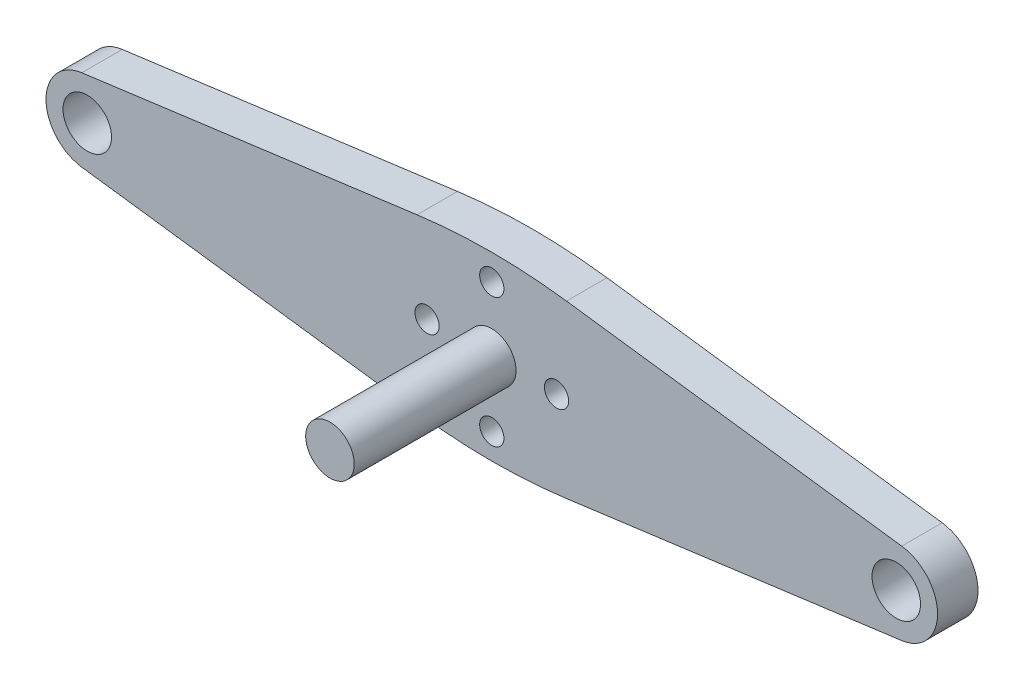
SolidWorks part; units mm, degrees
material "ABS"
ref_plane "Płaszczyzna przednia" through (0, 0, 0) normal (0, 0, 1) x (1, 0, 0)
ref_plane "Płaszczyzna górna" through (0, 0, 0) normal (0, 1, 0) x (1, 0, 0)
ref_plane "Płaszczyzna prawa" through (0, 0, 0) normal (1, 0, 0) x (0, 0, -1)
sketch "Szkic1" plane through (0, 0, 0) normal (0, 0, 1) x (1, 0, 0)
  line L0 (-44.521, 0) -> (57.4684, 0) construction
  line L1 (0, 0) -> (0, 26.3225) construction
  line L2 (-50.6729, 5.0557) -> (-9.2351, 10.5708)
  line L3 (-50.6729, -5.0557) -> (-9.2351, -10.5708)
  line L4 (50.6729, -5.0557) -> (9.2351, -10.5708)
  line L5 (50.6729, 5.0557) -> (9.2351, 10.5708)
  circle A0 centre (0, 0) radius 3
  circle A1 centre (0, 8) radius 1.5
  circle A2 centre (-8, 0) radius 1.5
  circle A3 centre (8, 0) radius 1.5
  circle A4 centre (0, -8) radius 1.5
  circle A5 centre (-50, 0) radius 3
  circle A6 centre (50, 0) radius 3
  arc A7 (-50.6729, 5.0557) -> (-50.6729, -5.0557) centre (-50, 0) ccw
  arc A8 (50.6729, 5.0557) -> (50.6729, -5.0557) centre (50, 0) cw
  arc A9 (-9.2351, 10.5708) -> (9.2351, 10.5708) centre (0, -58.8174) cw
  arc A10 (-9.2351, -10.5708) -> (9.2351, -10.5708) centre (0, 58.8174) ccw
  point P16 (0, 0)
  point P28 (0, 11.7999)
  point P31 (0, -11.7999)
  dimension "D1" = 4
  dimension "D2" = 50
  dimension "D3" = 6
  dimension "D4" = 6
  dimension "D5" = 3
  dimension "D6" = 16
  dimension "D7" = 70
extrude "Dodanie-wyciągnięcie1" add sketch "Szkic1" along normal blind 5
extrude "Dodanie-wyciągnięcie2" add sketch "Szkic1<2>" along normal blind 25 contours A0 region at (0, 0, 0)
sketch "Szkic1<2>" plane through (0, 0, 0) normal (0, 0, 1) x (1, 0, 0) same geometry as "Szkic1"
